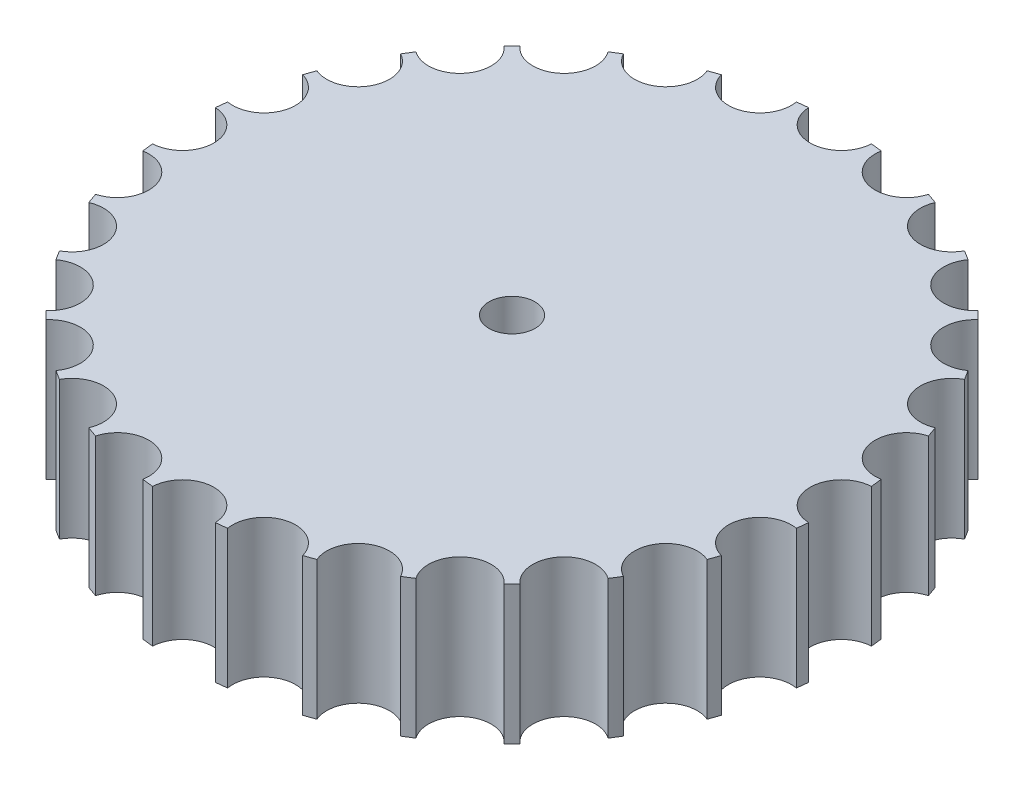
SolidWorks part; units mm, degrees
ref_plane "Front Plane" through (0, 0, 0) normal (0, 0, 1) x (1, 0, 0)
ref_plane "Top Plane" through (0, 0, 0) normal (0, 1, 0) x (1, 0, 0)
ref_plane "Right Plane" through (0, 0, 0) normal (1, 0, 0) x (0, 0, -1)
sketch "Sketch1" plane through (0, 0, 0) normal (0, 1, 0) x (1, 0, 0)
  arc A0 (-3.4, 35.5635) -> (3.4, 35.5635) centre (0, 35.7256) ccw
  circle A1 centre (0, 0) radius 35.7256
  arc A2 (4.5989, 35.4284) -> (11.2284, 33.9152) centre (7.9497, 34.8299) ccw
  arc A3 (12.3671, 33.5168) -> (18.4937, 30.5664) centre (15.5008, 32.1877) ccw
  arc A4 (19.5152, 29.9245) -> (24.8317, 25.6848) centre (22.2746, 27.9314) ccw
  arc A5 (25.6848, 24.8317) -> (29.9245, 19.5152) centre (27.9314, 22.2746) ccw
  arc A6 (30.5664, 18.4937) -> (33.5168, 12.3671) centre (32.1877, 15.5008) ccw
  arc A7 (33.9152, 11.2284) -> (35.4284, 4.5989) centre (34.8299, 7.9497) ccw
  arc A8 (35.5635, 3.4) -> (35.5635, -3.4) centre (35.7256, 0) ccw
  arc A9 (35.4284, -4.5989) -> (33.9152, -11.2284) centre (34.8299, -7.9497) ccw
  arc A10 (33.5168, -12.3671) -> (30.5664, -18.4937) centre (32.1877, -15.5008) ccw
  arc A11 (29.9245, -19.5152) -> (25.6848, -24.8317) centre (27.9314, -22.2746) ccw
  arc A12 (24.8317, -25.6848) -> (19.5152, -29.9245) centre (22.2746, -27.9314) ccw
  arc A13 (18.4937, -30.5664) -> (12.3671, -33.5168) centre (15.5008, -32.1877) ccw
  arc A14 (11.2284, -33.9152) -> (4.5989, -35.4284) centre (7.9497, -34.8299) ccw
  arc A15 (3.4, -35.5635) -> (-3.4, -35.5635) centre (0, -35.7256) ccw
  arc A16 (-4.5989, -35.4284) -> (-11.2284, -33.9152) centre (-7.9497, -34.8299) ccw
  arc A17 (-12.3671, -33.5168) -> (-18.4937, -30.5664) centre (-15.5008, -32.1877) ccw
  arc A18 (-19.5152, -29.9245) -> (-24.8317, -25.6848) centre (-22.2746, -27.9314) ccw
  arc A19 (-25.6848, -24.8317) -> (-29.9245, -19.5152) centre (-27.9314, -22.2746) ccw
  arc A20 (-30.5664, -18.4937) -> (-33.5168, -12.3671) centre (-32.1877, -15.5008) ccw
  arc A21 (-33.9152, -11.2284) -> (-35.4284, -4.5989) centre (-34.8299, -7.9497) ccw
  arc A22 (-35.5635, -3.4) -> (-35.5635, 3.4) centre (-35.7256, 0) ccw
  arc A23 (-35.4284, 4.5989) -> (-33.9152, 11.2284) centre (-34.8299, 7.9497) ccw
  arc A24 (-33.5168, 12.3671) -> (-30.5664, 18.4937) centre (-32.1877, 15.5008) ccw
  arc A25 (-29.9245, 19.5152) -> (-25.6848, 24.8317) centre (-27.9314, 22.2746) ccw
  arc A26 (-24.8317, 25.6848) -> (-19.5152, 29.9245) centre (-22.2746, 27.9314) ccw
  arc A27 (-18.4937, 30.5664) -> (-12.3671, 33.5168) centre (-15.5008, 32.1877) ccw
  arc A28 (-11.2284, 33.9152) -> (-4.5989, 35.4284) centre (-7.9497, 34.8299) ccw
  circle A29 centre (0, 0) radius 2.5
  point P8 (0, 32.3218)
  point P90 (0, 0)
  dimension "D2" = 8
  dimension "D4" = 5
  dimension "D1" = 3.4039
  dimension "D3" = 28
extrude "Boss-Extrude1" add sketch "Sketch1" along normal blind 15 contours A28 A1 A27 A26 A25 A24 A23 A22 A21 A20 A19 A18 A17 A16 A15 A14 A13 A12 A11 A10 A9 A8 A7 A6 A5 A4 A3 region at (0, 0, -31.3159)
